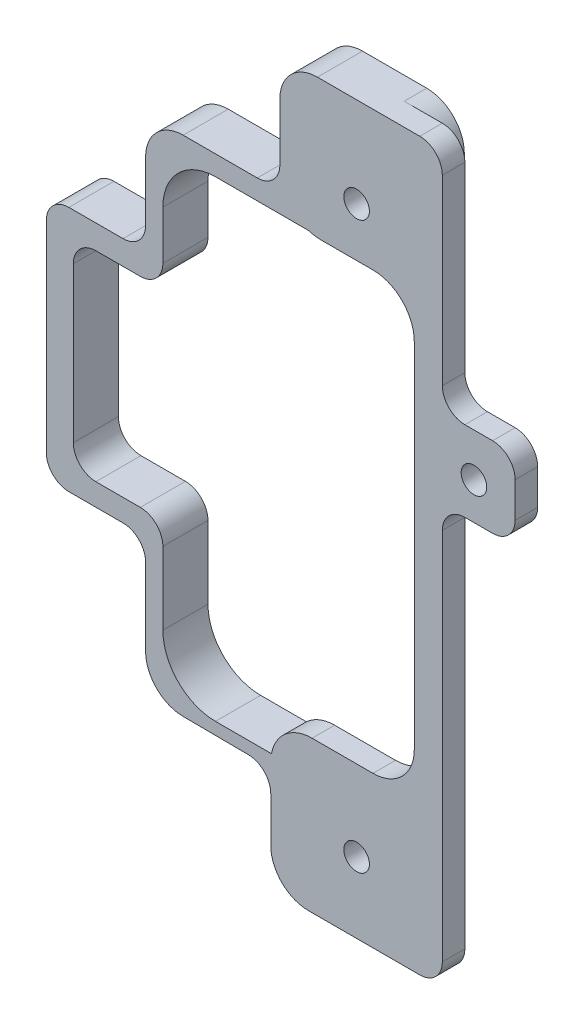
SolidWorks part; units mm, degrees
ref_plane "Plan de face" through (0, 0, 0) normal (0, 0, 1) x (1, 0, 0)
ref_plane "Plan de dessus" through (0, 0, 0) normal (0, 1, 0) x (1, 0, 0)
ref_plane "Plan de droite" through (0, 0, 0) normal (1, 0, 0) x (0, 0, -1)
sketch "Esquisse1" plane through (0, 0, 0) normal (0, 0, 1) x (1, 0, 0)
  line L0 (-101.8864, 22.7193) -> (-68.2286, 22.7193) construction
  line L1 (-68.0864, 83.4017) -> (-68.0864, 71.4017) construction
  line L2 (-118.8906, -27.2807) -> (-47.3665, -27.2807) construction
  line L3 (-120.7144, 72.7193) -> (-56.8564, 72.7193) construction
  line L4 (-83.4864, -42.5983) -> (-83.4864, 89.4017) construction
  line L5 (-56.8564, -27.2807) -> (-56.8564, 72.7193) construction
  line L6 (-110.1164, -27.2807) -> (-110.1164, 72.7193) construction
  line L7 (-59.2664, -27.2807) -> (-59.2664, 72.7193) construction
  line L8 (-56.8564, -13.2807) -> (-110.1164, -13.2807) construction
  line L9 (-64.3564, -27.2807) -> (-64.3564, 72.7193) construction
  line L10 (-110.1164, 36.7193) -> (-56.8564, 36.7193) construction
  line L11 (-56.8564, 66.9393) -> (-110.1164, 66.9393) construction
  line L12 (-91.8564, -27.2807) -> (-91.8564, 72.7193) construction
  line L13 (-107.4664, -27.2807) -> (-107.4664, 72.7193) construction
  line L14 (-56.8564, -14.5207) -> (-110.1164, -14.5207) construction
  line L15 (-110.1164, 60.7193) -> (-56.8564, 60.7193) construction
  line L16 (-117.6801, 66.9393) -> (-117.6801, 59.6951)
  line L17 (-112.1801, 54.1951) -> (-105.2942, 54.1951)
  line L18 (-99.7942, 48.6951) -> (-99.7942, 35.9308)
  line L20 (-105.2942, -3.8078) -> (-113.3906, -3.8078)
  line L21 (-118.8906, -9.3078) -> (-118.8906, -18.422)
  line L22 (-113.3906, -23.922) -> (-99.7942, -23.922)
  line L23 (-99.0637, -23.922) -> (-99.7942, -23.922)
  line L24 (-96.0637, -20.922) -> (-96.0637, 28.8053)
  line L25 (-93.0637, 31.8053) -> (-89.3777, 31.8053)
  line L28 (-99.0637, 72.7193) -> (-112.1801, 72.7193)
  line L29 (-117.6801, 67.2193) -> (-117.6801, 66.9393)
  line L30 (-86.3777, 34.8053) -> (-86.3777, 39.4789)
  line L31 (-89.3777, 42.4789) -> (-93.0637, 42.4789)
  line L32 (-96.0637, 45.4789) -> (-96.0637, 69.7193)
  line L36 (-99.7942, 12.91) -> (-99.7942, 1.6922)
  line L42 (-99.7942, 12.91) -> (-99.7942, 35.9308)
  arc A1 (-99.0637, -23.922) -> (-96.0637, -20.922) centre (-99.0637, -20.922) ccw
  circle A3 centre (-91.8564, 36.7193) radius 1.7
  arc A4 (-96.0637, 69.7193) -> (-99.0637, 72.7193) centre (-99.0637, 69.7193) ccw
  arc A5 (-112.1801, 72.7193) -> (-117.6801, 67.2193) centre (-112.1801, 67.2193) ccw
  circle A6 centre (-107.4664, -14.5207) radius 1.7
  circle A7 centre (-107.4664, 60.7193) radius 1.7
  arc A8 (-117.6801, 59.6951) -> (-112.1801, 54.1951) centre (-112.1801, 59.6951) ccw
  arc A9 (-105.2942, 54.1951) -> (-99.7942, 48.6951) centre (-105.2942, 48.6951) cw
  arc A10 (-99.7942, 1.6922) -> (-105.2942, -3.8078) centre (-105.2942, 1.6922) cw
  arc A11 (-113.3906, -3.8078) -> (-118.8906, -9.3078) centre (-113.3906, -9.3078) ccw
  arc A12 (-118.8906, -18.422) -> (-113.3906, -23.922) centre (-113.3906, -18.422) ccw
  arc A13 (-93.0637, 42.4789) -> (-96.0637, 45.4789) centre (-93.0637, 45.4789) cw
  arc A14 (-86.3777, 39.4789) -> (-89.3777, 42.4789) centre (-89.3777, 39.4789) ccw
  arc A15 (-96.0637, 28.8053) -> (-93.0637, 31.8053) centre (-93.0637, 28.8053) cw
  arc A16 (-89.3777, 31.8053) -> (-86.3777, 34.8053) centre (-89.3777, 34.8053) ccw
  point P61 (-117.6801, 72.7193)
  point P68 (-99.7942, -3.8078)
  point P79 (-83.4864, -3.8078)
  point P82 (-83.4864, 60.7193)
  point P87 (-48.6904, 72.7193)
  point P98 (-83.4864, 30.4308)
  point P101 (-64.3564, 18.41)
  point P104 (-64.3564, 30.4308)
  point P109 (-99.7942, 18.41)
  point P116 (-99.7942, 30.4308)
  dimension "D1" = 5.5
  dimension "D2" = 3
extrude "Boss.-Extru.1" add sketch "Esquisse1" along normal blind 3
sketch "Esquisse2" plane through (0, 0, 0) normal (0, 0, -1) x (-1, 0, 0)
  line L1 (133.2464, 87.1044) -> (133.2464, 37.9772) construction
  line L3 (133.2464, -8.2937) -> (104.1367, -8.2937) construction
  line L4 (133.2464, 54.4563) -> (104.1367, 54.4563) construction
  line L5 (126.2464, -8.2937) -> (126.2464, -1.2937) construction
  line L6 (126.2464, -1.2937) -> (133.2464, -1.2937) construction
  line L7 (126.2464, 54.4563) -> (126.2464, 47.4563) construction
  line L8 (126.2464, 47.4563) -> (133.2464, 47.4563) construction
  line L13 (121.8677, -9.9467) -> (130.5846, -9.8801)
  line L14 (120.6801, 57.0999) -> (130.5464, 57.0999)
  line L23 (126.2464, 54.4563) -> (104.1367, 54.4563)
  line L25 (133.2464, 47.4563) -> (133.2464, 40.9772)
  line L26 (104.1367, 72.7193) -> (112.6801, 72.7193)
  line L27 (138.5464, 8.4156) -> (145.7527, 8.4156)
  line L29 (148.7527, 11.4156) -> (148.7527, 38.1792)
  line L30 (133.2464, 34.4495) -> (133.2464, -42.3137) construction
  line L31 (99.1367, -18.922) -> (99.1367, -13.2937)
  line L32 (117.6801, 67.7193) -> (117.6801, 60.0999)
  line L33 (99.1367, 59.4563) -> (99.1367, 67.7193)
  line L34 (104.1367, -8.2937) -> (126.2464, -8.2937)
  line L35 (135.5464, -24.0475) -> (135.5464, 64.4693) construction
  line L37 (133.2464, 8.3631) -> (133.2464, -1.2937)
  line L38 (104.1367, -23.922) -> (113.8906, -23.922)
  line L39 (118.8906, -18.922) -> (118.8906, -12.9467)
  line L40 (118.8906, -9.3078) -> (118.8906, -18.422) construction
  line L41 (145.7527, 41.1792) -> (138.5464, 41.1792)
  line L42 (136.2464, 11.3631) -> (142.1623, 11.3631)
  line L43 (145.1623, 14.3631) -> (145.1623, 34.9772)
  line L44 (142.1623, 37.9772) -> (136.2464, 37.9772)
  line L47 (135.5464, -4.8802) -> (135.5464, 5.4156)
  line L57 (135.5464, 44.1792) -> (135.5464, 52.0999)
  arc A0 (133.2464, -1.2937) -> (126.2464, -8.2937) centre (126.2464, -1.2937) cw
  arc A1 (133.2464, 47.4563) -> (126.2464, 54.4563) centre (126.2464, 47.4563) ccw
  arc A2 (113.8906, -23.922) -> (118.8906, -18.922) centre (113.8906, -18.922) ccw
  arc A3 (99.1367, -18.922) -> (104.1367, -23.922) centre (104.1367, -18.922) ccw
  arc A4 (99.1367, -13.2937) -> (104.1367, -8.2937) centre (104.1367, -13.2937) cw
  arc A5 (148.7527, 38.1792) -> (145.7527, 41.1792) centre (145.7527, 38.1792) ccw
  arc A6 (138.5464, 41.1792) -> (135.5464, 44.1792) centre (138.5464, 44.1792) cw
  arc A7 (136.2464, 37.9772) -> (133.2464, 40.9772) centre (136.2464, 40.9772) cw
  arc A8 (145.1623, 34.9772) -> (142.1623, 37.9772) centre (142.1623, 34.9772) ccw
  arc A9 (142.1623, 11.3631) -> (145.1623, 14.3631) centre (142.1623, 14.3631) ccw
  arc A10 (145.7527, 8.4156) -> (148.7527, 11.4156) centre (145.7527, 11.4156) ccw
  arc A11 (133.2464, 8.3631) -> (136.2464, 11.3631) centre (136.2464, 8.3631) cw
  arc A12 (135.5464, 52.0999) -> (130.5464, 57.0999) centre (130.5464, 52.0999) ccw
  arc A13 (138.5464, 8.4156) -> (135.5464, 5.4156) centre (138.5464, 5.4156) ccw
  arc A14 (99.1367, 59.4563) -> (104.1367, 54.4563) centre (104.1367, 59.4563) ccw
  arc A15 (130.5846, -9.8801) -> (135.5464, -4.8802) centre (130.5464, -4.8802) ccw
  arc A16 (99.1367, 67.7193) -> (104.1367, 72.7193) centre (104.1367, 67.7193) cw
  arc A17 (112.6801, 72.7193) -> (117.6801, 67.7193) centre (112.6801, 67.7193) cw
  circle A18 centre (107.4664, -14.5207) radius 5.2
  circle A19 centre (107.4664, 60.7193) radius 5.2
  arc A20 (118.8906, -12.9467) -> (121.8677, -9.9467) centre (121.8906, -12.9467) cw
  arc A21 (117.6801, 60.0999) -> (120.6801, 57.0999) centre (120.6801, 60.0999) ccw
  point P34 (135.5464, 57.0999)
  point P37 (132.9964, 22.9063)
  point P39 (99.1367, -8.2937)
  point P43 (132.9964, 22.9063)
  point P45 (133.2464, 29.4495)
  point P50 (133.2464, 16.3631)
  point P62 (111.5444, -10.0296)
  point P71 (64.0892, -10.4396)
  point P74 (135.5464, 26.097)
  point P75 (134.7715, 19.7156)
  point P91 (118.8906, -9.9695)
  point P107 (135.5464, 19.7156)
  point P110 (135.5464, -9.8421)
  dimension "D13" = 5
  dimension "D14" = 3
  dimension "D15" = 3
  dimension "D16" = 5
  dimension "D18" = 3
  dimension "D4" = 62.75
  dimension "D5" = 7
  dimension "D6" = 7
  dimension "D7" = 7
  dimension "D8" = 7
  dimension "D17" = 2.3
extrude "Boss.-Extru.2" add sketch "Esquisse2" along normal blind 3 and the other way blind 3
